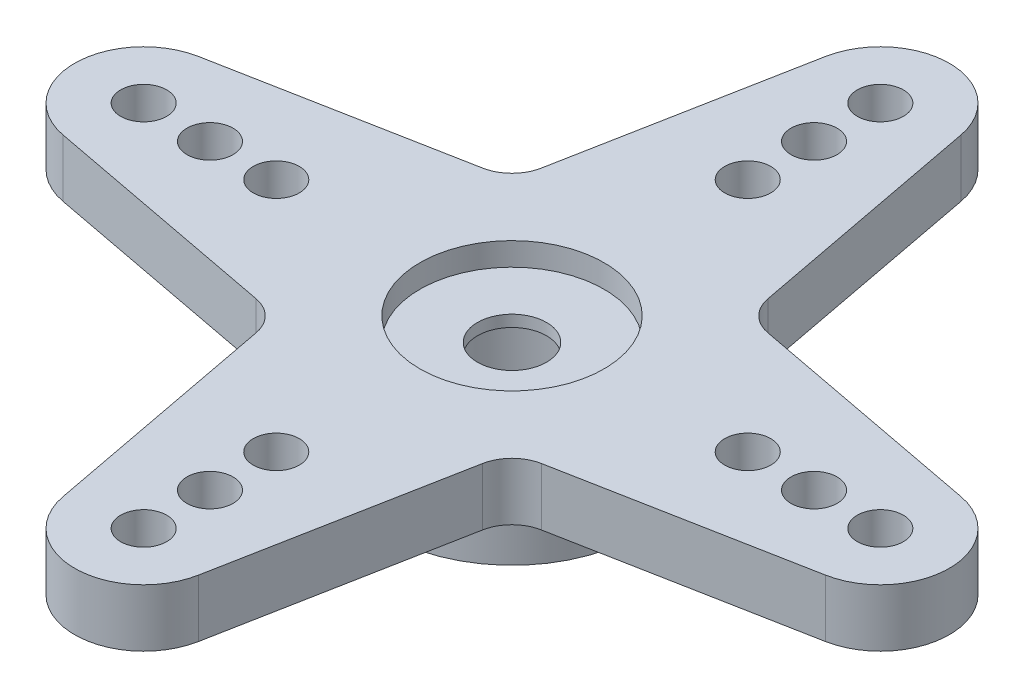
SolidWorks part; units mm, degrees
ref_plane "Front Plane" through (0, 0, 0) normal (0, 0, 1) x (1, 0, 0)
ref_plane "Top Plane" through (0, 0, 0) normal (0, 1, 0) x (1, 0, 0)
ref_plane "Right Plane" through (0, 0, 0) normal (1, 0, 0) x (0, 0, -1)
sketch "Sketch1" plane through (0, 0, 0) normal (0, 1, 0) x (1, 0, 0)
  line L0 (-1000, 0) -> (49000, 0) construction
  line L1 (0, -1000) -> (0, 49000) construction
  line L2 (-3.9044, 4.9148) -> (-2.3393, 13.1449)
  line L3 (3.9044, 4.9148) -> (2.3393, 13.1449)
  line L4 (4.9148, 3.9044) -> (13.1449, 2.3393)
  line L5 (4.9148, -3.9044) -> (13.1449, -2.3393)
  line L6 (3.9044, -4.9148) -> (2.3393, -13.1449)
  line L7 (-3.9044, -4.9148) -> (-2.3393, -13.1449)
  line L8 (-4.0659, 4.0659) -> (-4.0659, -4.0659) construction
  line L9 (-4.0659, 4.0659) -> (4.0659, 4.0659) construction
  line L10 (-4.0659, -4.0659) -> (4.0659, -4.0659) construction
  line L11 (4.0659, 4.0659) -> (4.0659, -4.0659) construction
  line L12 (-4.9148, -3.9044) -> (-13.1449, -2.3393)
  line L13 (-4.9148, 3.9044) -> (-13.1449, 2.3393)
  circle A0 centre (0, 0) radius 1.1906
  circle A1 centre (0, 0) radius 5.75 construction
  arc A2 (-2.3393, 13.1449) -> (2.3393, 13.1449) centre (0, 12.7) cw
  circle A3 centre (0, 12.7) radius 0.7937
  circle A4 centre (0, 10.414) radius 0.7937
  circle A5 centre (0, 8.128) radius 0.7937
  arc A6 (13.1449, 2.3393) -> (13.1449, -2.3393) centre (12.7, 0) cw
  circle A7 centre (12.7, 0) radius 0.7937
  circle A8 centre (10.414, 0) radius 0.7937
  circle A9 centre (8.128, 0) radius 0.7937
  arc A10 (2.3393, -13.1449) -> (-2.3393, -13.1449) centre (0, -12.7) cw
  circle A11 centre (0, -12.7) radius 0.7937
  circle A12 centre (0, -10.414) radius 0.7937
  circle A13 centre (0, -8.128) radius 0.7937
  arc A14 (-13.1449, -2.3393) -> (-13.1449, 2.3393) centre (-12.7, 0) cw
  circle A15 centre (-12.7, 0) radius 0.7937
  circle A16 centre (-10.414, 0) radius 0.7937
  circle A17 centre (-8.128, 0) radius 0.7937
  arc A18 (3.9044, 4.9148) -> (4.9148, 3.9044) centre (5.1521, 5.1521) ccw
  arc A19 (-3.9044, -4.9148) -> (-4.9148, -3.9044) centre (-5.1521, -5.1521) ccw
  arc A20 (-3.9044, 4.9148) -> (-4.9148, 3.9044) centre (-5.1521, 5.1521) cw
  arc A21 (3.9044, -4.9148) -> (4.9148, -3.9044) centre (5.1521, -5.1521) cw
  dimension "D1" = 11.5
  dimension "D2" = 2.3813
  dimension "D3" = 2.3813
  dimension "D5" = 1.5875
  dimension "D8" = 1.27
  dimension "D9" = 1.27
  dimension "D10" = 1.27
  dimension "D11" = 1.27
  dimension "D4" = 12.7
  dimension "D6" = 3
  dimension "D7" = 4
extrude "Boss-Extrude1" add sketch "Sketch1" along normal blind 1.9844
sketch "Sketch2" plane through (0, 1.9844, 0) normal (0, 1, 0) x (1, 0, 0)
  circle A0 centre (0, 0) radius 3.175
  dimension "D1" = 6.35
extrude "Cut-Extrude1" cut sketch "Sketch2" against normal blind 0.7937
sketch "Sketch3" plane through (0, 0, 0) normal (0, -1, 0) x (1, 0, 0)
  circle A0 centre (0, 0) radius 4.3656
  dimension "D1" = 8.7312
extrude "Boss-Extrude2" add sketch "Sketch3" along normal blind 2.3813
sketch "Sketch4" plane through (0, -2.3813, 0) normal (0, -1, 0) x (1, 0, 0)
  circle A0 centre (0, 0) radius 2.7781
  dimension "D1" = 5.5562
extrude "Cut-Extrude2" cut sketch "Sketch4" against normal blind 3.175
